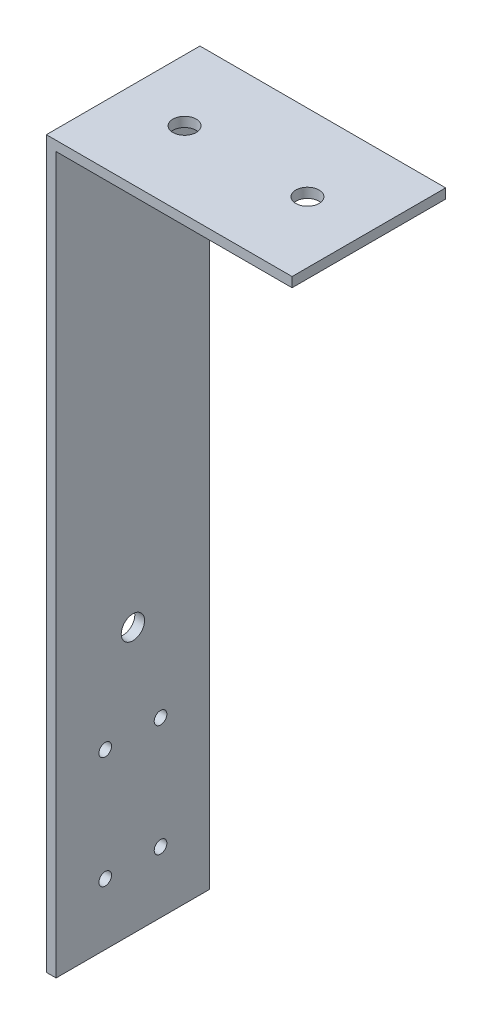
SolidWorks part; units mm, degrees
ref_plane "Front Plane" through (0, 0, 0) normal (0, 0, 1) x (1, 0, 0)
ref_plane "Top Plane" through (0, 0, 0) normal (0, 1, 0) x (1, 0, 0)
ref_plane "Right Plane" through (0, 0, 0) normal (1, 0, 0) x (0, 0, -1)
sketch "Sketch2" plane through (0, 0, 0) normal (0, 0, 1) x (1, 0, 0)
  line L0 (0, 0) -> (0, 118.1)
  line L1 (0, 118.1) -> (40, 118.1)
  line L2 (1.5875, 0) -> (1.5875, 116.5125)
  line L3 (1.5875, 116.5125) -> (40, 116.5125)
  line L4 (40, 118.1) -> (40, 116.5125)
  line L5 (0, 0) -> (1.5875, 0)
  dimension "D1" = 40
  dimension "D2" = 118.1
  dimension "D3" = 1.5875
extrude "Boss-Extrude1" add sketch "Sketch2" along normal blind 25
hole_wizard "#6 Clearance Hole1" positions "Sketch4" profile "Sketch3" hole size "#6" standard "ANSI Inch" end condition through all
sketch "Sketch4" plane through (0, 118.1, 0) normal (0, 1, 0) x (1, 0, 0)
  line L0 (40, 0) -> (0, 0) construction
  line L1 (0, -25) -> (0, 0) construction
  point P0 (10, -12.5)
  point P2 (30, -12.5)
  dimension "D1" = 12.5
  dimension "D2" = 10
  dimension "D3" = 20
sketch "Sketch3" plane through (10, 118.1, 12.5) normal (1, 0, 0) x (0, 0, 1)
  line L0 (0, 0) -> (0, 118.1)
  line L1 (0, 118.1) -> (1.8986, 118.1)
  line L2 (1.8986, 118.1) -> (1.8986, 0)
  line L5 (1.8986, 0) -> (0, 0)
  line L11 (0, -6.35) -> (0, 107.95) construction
  dimension "Thru Hole Dia." = 3.7973
  dimension "Thru Hole Depth" = 118.1
hole_wizard "#1 Clearance Hole2" positions "Sketch8" profile "Sketch7" hole size "#1" standard "ANSI Inch" end condition through all
sketch "Sketch8" plane through (0, 0, 0) normal (-1, 0, 0) x (0, 0, 1)
  line L0 (25, 0) -> (0, 0) construction
  line L1 (25, 118.1) -> (25, 0) construction
  line L2 (0, 0) -> (0, 116.5125) construction
  point P0 (17, 10)
  point P2 (17, 28.2)
  point P10 (8, 10)
  point P12 (8, 28.2)
  dimension "D1" = 10
  dimension "D2" = 8
  dimension "D3" = 18.2
  dimension "D4" = 8
sketch "Sketch7" plane through (0, 10, 17) normal (0, 1, 0) x (0, 0, 1)
  line L0 (0, 0) -> (0, 40)
  line L1 (0, 40) -> (1.0287, 40)
  line L2 (1.0287, 40) -> (1.0287, 0)
  line L5 (1.0287, 0) -> (0, 0)
  line L11 (0, -6.35) -> (0, 107.95) construction
  dimension "Thru Hole Dia." = 2.0574
  dimension "Thru Hole Depth" = 40
hole_wizard "#6 Clearance Hole2" positions "Sketch10" profile "Sketch9" hole size "#6" standard "ANSI Inch" end condition through all
sketch "Sketch10" plane through (0, 0, 0) normal (-1, 0, 0) x (0, 0, 1)
  line L0 (0, 118.1) -> (0, 0) construction
  circle A0 centre (17, 28.2) radius 1.0287 construction
  point P0 (12.5, 43.2)
  dimension "D1" = 15
  dimension "D2" = 12.5
sketch "Sketch9" plane through (0, 43.2, 12.5) normal (0, 1, 0) x (0, 0, 1)
  line L0 (0, 0) -> (0, 40)
  line L1 (0, 40) -> (1.8986, 40)
  line L2 (1.8986, 40) -> (1.8986, 0)
  line L5 (1.8986, 0) -> (0, 0)
  line L11 (0, -6.35) -> (0, 107.95) construction
  dimension "Thru Hole Dia." = 3.7973
  dimension "Thru Hole Depth" = 40
